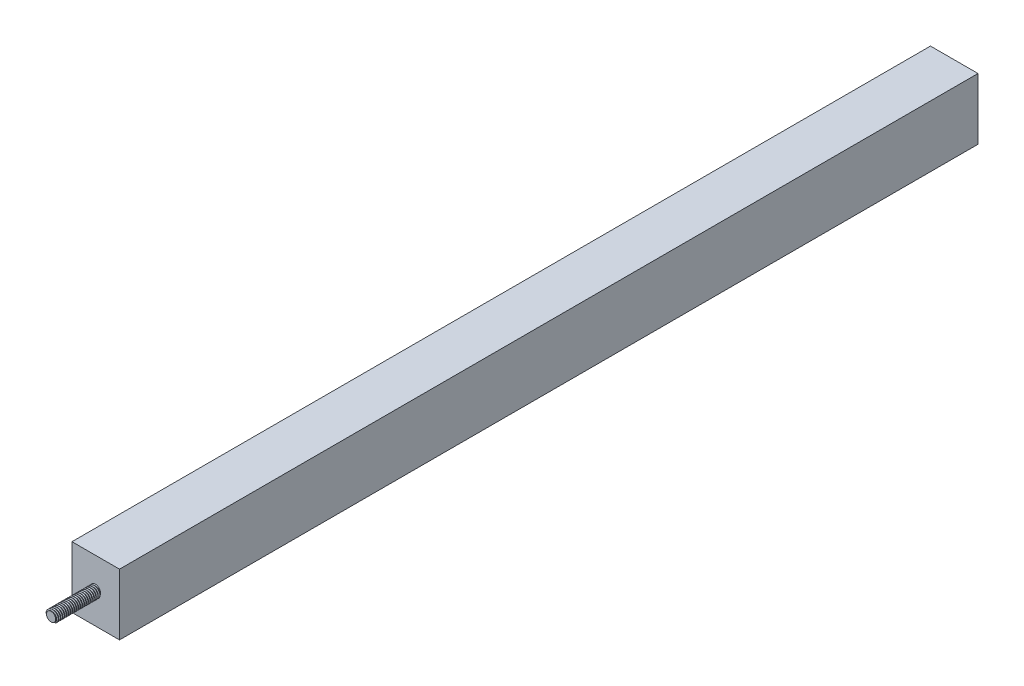
SolidWorks part; units mm, degrees
ref_plane "Front Plane" through (0, 0, 0) normal (0, 0, 1) x (1, 0, 0)
ref_plane "Top Plane" through (0, 0, 0) normal (0, 1, 0) x (1, 0, 0)
ref_plane "Right Plane" through (0, 0, 0) normal (1, 0, 0) x (0, 0, -1)
sketch "Sketch1" plane through (0, 0, 0) normal (0, 0, 1) x (1, 0, 0)
  line L1 (0, 0) -> (25.4, 0)
  line L2 (0, 0) -> (0, 32.766)
  line L3 (0, 32.766) -> (25.4, 32.766)
  line L4 (25.4, 0) -> (25.4, 32.766)
  dimension "D1" = 25.4
  dimension "D2" = 32.766
extrude "Boss-Extrude1" add sketch "Sketch1" against normal blind 482.6
sketch "Sketch2" plane through (0, 0, 0) normal (0, 0, 1) x (1, 0, 0)
  line L0 (25.4, 32.766) -> (0, 32.766) construction
  line L1 (25.4, 0) -> (25.4, 32.766) construction
  line L3 (0, 32.766) -> (25.4, 32.766)
  line L4 (0, 32.766) -> (0, 0)
  line L5 (0, 0) -> (25.4, 0)
  line L6 (25.4, 32.766) -> (25.4, 0)
  circle A0 centre (12.7, 16.383) radius 2.4574
  dimension "D1" = 4.9149
  dimension "D2" = 16.383
  dimension "D3" = 12.7
extrude "Cut-Extrude2" cut sketch "Sketch2" against normal blind 23.876
thread "Thread2" pitch 1.0583 method extrude profile "Thread Profile2" start angle 0, offset 0, length 0, pitch 1.0583, diameter 4.9149
ref_plane "Plane2" through (10.2425, 16.383, 0) normal (0, -1, 0) x (-1, 0, 0)
sketch "Thread Profile2" plane through (10.2425, 16.383, 0) normal (0, -1, 0) x (-1, 0, 0)
  line L0 (0, 0) -> (0, 1.0583) construction
  line L1 (0, 0) -> (0.5728, 0.3307)
  line L2 (0.5728, 0.3307) -> (0.5728, 0.463)
  line L3 (0.5728, 0.463) -> (0, 0.7937)
  line L4 (0.5728, 0.3969) -> (0, 0.3969) construction
  line L11 (0, 0) -> (0, 0.7937)
  point P2 (0, 0)
  dimension "Pitch" = 1.0583
  dimension "Profile_Angle" = 60
  dimension "Profile_Land" = 0.1323
  dimension "Profile_Height" = 0.5728
ref_plane "Plane3" through (0, 0, -253.238) normal (0, 0, -1) x (-1, 0, 0)
